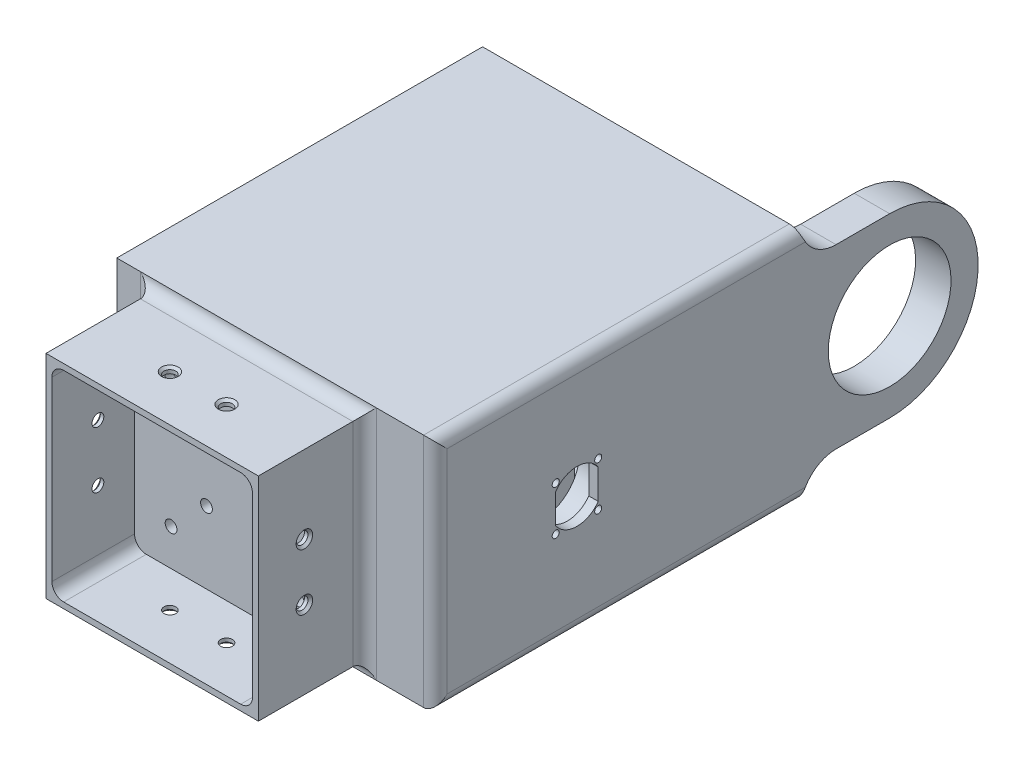
SolidWorks part; units mm, degrees
ref_plane "Front Plane" through (0, 0, 0) normal (0, 0, 1) x (1, 0, 0)
ref_plane "Top Plane" through (0, 0, 0) normal (0, 1, 0) x (1, 0, 0)
ref_plane "Right Plane" through (0, 0, 0) normal (1, 0, 0) x (0, 0, -1)
sketch "Sketch2" plane through (0, 0, 0) normal (0, 0, 1) x (1, 0, 0)
  line L1 (-45, 45) -> (45, 45)
  line L2 (-45, 45) -> (-45, -45)
  line L3 (-45, -45) -> (45, -45)
  line L4 (45, 45) -> (45, -45)
  line L5 (-45, 45) -> (45, -45) construction
  line L6 (-45, -45) -> (45, 45) construction
  point P0 (0, 0)
  dimension "D1" = 90
extrude "Boss-Extrude1" add sketch "Sketch2" along normal blind 45
sketch "Sketch3" plane through (0, 0, 45) normal (0, 0, 1) x (1, 0, 0)
  line L1 (-42.5, 42.5) -> (42.5, 42.5)
  line L2 (-42.5, 42.5) -> (-42.5, -42.5)
  line L3 (-42.5, -42.5) -> (42.5, -42.5)
  line L4 (42.5, 42.5) -> (42.5, -42.5)
  line L5 (-42.5, 42.5) -> (42.5, -42.5) construction
  line L6 (-42.5, -42.5) -> (42.5, 42.5) construction
  point P0 (0, 0)
  dimension "80" = 85
extrude "Cut-Extrude1" cut sketch "Sketch3" against normal blind 35
sketch "Sketch4" plane through (-45, 0, 0) normal (-1, 0, 0) x (0, 0, 1)
  line L0 (0, 45) -> (0, -45) construction
  line L3 (45, -45) -> (0, -45) construction
  circle A0 centre (25.5, 12) radius 2.5
  circle A1 centre (25.5, -12) radius 2.5
  dimension "D2" = 5
  dimension "D1" = 25.5
  dimension "D3" = 24
  dimension "D4" = 33
extrude "Cut-Extrude2" cut sketch "Sketch4" against normal through all
fillet "Fillet1" radius 5 4 edges at (42.5, -42.5, 27.5) (42.5, 42.5, 27.5) (-42.5, 42.5, 27.5) (-42.5, -42.5, 27.5)
sketch "Sketch5" plane through (0, 45, 0) normal (0, 1, 0) x (1, 0, 0)
  line L0 (45, 0) -> (-45, 0) construction
  line L1 (-45, -45) -> (-45, 0) construction
  circle A0 centre (-12, -25.5) radius 2.5
  circle A1 centre (12, -25.5) radius 2.5
  dimension "D3" = 5
  dimension "D1" = 24
  dimension "D2" = 25.5
  dimension "D4" = 33
extrude "Cut-Extrude3" cut sketch "Sketch5" against normal through all
chamfer "Chamfer1" distance 1 angle 45 8 edges at (12, 45, 28) (-12, 45, 28) (45, -14.5, 25.5) (45, 9.5, 25.5) (12, -45, 28) (-12, -45, 28) (-45, 9.5, 25.5) (-45, -14.5, 25.5)
sketch "Sketch7" plane through (0, 0, 0) normal (0, 0, -1) x (-1, 0, 0)
  line L1 (-75, 50) -> (75, 50)
  line L2 (-75, 50) -> (-75, -50)
  line L3 (-75, -50) -> (75, -50)
  line L4 (75, 50) -> (75, -50)
  line L5 (-75, 50) -> (75, -50) construction
  line L6 (-75, -50) -> (75, 50) construction
  point P0 (0, 0)
  dimension "D1" = 150
  dimension "D2" = 100
extrude "Boss-Extrude2" add sketch "Sketch7" along normal blind 155
sketch "Sketch8" plane through (0, 0, -155) normal (0, 0, -1) x (-1, 0, 0)
  line L1 (-60, 35) -> (60, 35)
  line L2 (-60, 35) -> (-60, -35)
  line L3 (-60, -35) -> (60, -35)
  line L4 (60, 35) -> (60, -35)
  line L5 (-60, 35) -> (60, -35) construction
  line L6 (-60, -35) -> (60, 35) construction
  point P0 (0, 0)
  dimension "D1" = 120
  dimension "D2" = 70
extrude "Cut-Extrude5" cut sketch "Sketch8" against normal blind 135
sketch "Sketch9" plane through (0, 0, 10) normal (0, 0, 1) x (1, 0, 0)
  line L0 (-41.0355, 41.0355) -> (41.0355, -41.0355) construction
  line L1 (41.0355, 41.0355) -> (-41.0355, -41.0355) construction
  line L2 (-42.5, 37.5) -> (-42.5, -37.5) construction
  arc A0 (-37.5, 42.5) -> (-42.5, 37.5) centre (-37.5, 37.5) ccw construction
  arc A1 (37.5, -42.5) -> (42.5, -37.5) centre (37.5, -37.5) ccw construction
  arc A2 (42.5, 37.5) -> (37.5, 42.5) centre (37.5, 37.5) ccw construction
  arc A3 (-42.5, -37.5) -> (-37.5, -42.5) centre (-37.5, -37.5) ccw construction
  circle A4 centre (-27, 27) radius 2.5
  circle A5 centre (27, 27) radius 2.5
  circle A6 centre (27, -27) radius 2.5
  circle A7 centre (-27, -27) radius 2.5
  circle A8 centre (-12, 12) radius 2.5
  circle A9 centre (12, 12) radius 2.5
  circle A10 centre (-12, -12) radius 2.5
  circle A11 centre (12, -12) radius 2.5
  dimension "D1" = 5
  dimension "D2" = 15.5
  dimension "D3" = 30.5
extrude "Cut-Extrude6" cut sketch "Sketch9" against normal through all
fillet "Fillet3" radius 5 4 edges at (0, -45, 0) (0, 45, 0) (-45, 0, 0) (45, 0, 0)
sketch "Sketch12" plane through (0, 0, -155) normal (0, 0, -1) x (-1, 0, 0)
  line L6 (-75, 0) -> (-60, 0) construction
  line L7 (-75, 50) -> (-75, -50) construction
  line L8 (-60, 35) -> (-60, -35) construction
  line L10 (-60, -37.5) -> (-75, -37.5)
  line L11 (-60, -37.5) -> (-60, 37.5)
  line L12 (-60, 37.5) -> (-75, 37.5)
  line L13 (-75, -37.5) -> (-75, 37.5)
  line L14 (-60, -37.5) -> (-75, 37.5) construction
  line L15 (-60, 37.5) -> (-75, -37.5) construction
  point P7 (-67.5, 0)
  dimension "D1" = 15
  dimension "D2" = 75
extrude "Boss-Extrude3" add sketch "Sketch12" along normal blind 75
sketch "Sketch13" plane through (60, 0, 0) normal (-1, 0, 0) x (0, 0, 1)
  line L0 (-230, -37.5) -> (-230, 37.5) construction
  line L1 (-230, 37.5) -> (-155, 37.5) construction
  circle A0 centre (-192.5, 0) radius 26
  dimension "D1" = 52
  dimension "D2" = 37.5
  dimension "D3" = 37.5
extrude "Cut-Extrude8" cut sketch "Sketch13" against normal blind 75
sketch "Sketch14" plane through (75, 0, 0) normal (1, 0, 0) x (0, 0, -1)
  line L0 (230, 37.5) -> (155, 37.5) construction
  line L1 (230, -37.5) -> (155, -37.5) construction
  line L2 (230, 37.5) -> (230, -37.5) construction
  arc A0 (192.5, 37.5) -> (192.5, -37.5) centre (192.5, 0) cw
  circle A1 centre (192.5, 0) radius 26 construction
  point P9 (230, 0)
extrude "Cut-Extrude9" cut sketch "Sketch14" against normal blind 75 and the other way through all
fillet "Fillet6" radius 15 2 edges at (67.5, -37.5, -155) (67.5, 37.5, -155)
fillet "Fillet7" radius 5 3 edges at (75, 0, 0) (75, -50, -77.5) (75, 50, -77.5)
sketch "Sketch15" plane through (0, 0, -155) normal (0, 0, -1) x (-1, 0, 0)
  line L0 (75, 50) -> (-60, 50) construction
  line L5 (75, -50) -> (60, -50)
  line L6 (75, -50) -> (75, 50)
  line L7 (75, 50) -> (60, 50)
  line L8 (60, -50) -> (60, 50)
  dimension "D1" = 15
extrude "Cut-Extrude11" cut sketch "Sketch15" against normal up to next
sketch "Sketch16" plane through (-60, 0, 0) normal (-1, 0, 0) x (0, 0, 1)
  line L0 (0, -50) -> (0, 50) construction
  line L1 (0, -50) -> (-155, -50) construction
  line L2 (0, 0) -> (-20, 0) construction
  line L3 (-20, -35) -> (-20, 35) construction
  circle A0 centre (-7.5, -42.5) radius 2
  circle A5 centre (-42.5, -42.5) radius 2
  circle A6 centre (-77.5, -42.5) radius 2
  circle A7 centre (-112.5, -42.5) radius 2
  circle A8 centre (-147.5, -42.5) radius 2
  circle A9 centre (-147.5, 42.5) radius 2
  circle A10 centre (-112.5, 42.5) radius 2
  circle A11 centre (-77.5, 42.5) radius 2
  circle A12 centre (-42.5, 42.5) radius 2
  circle A13 centre (-7.5, 42.5) radius 2
  circle A14 centre (-7.5, 12.5) radius 2
  circle A15 centre (-7.5, -17.5) radius 2
  dimension "D4" = 4
  dimension "D1" = 7.5
  dimension "D2" = 7.5
  dimension "D5" = 140
  dimension "D7" = 60
  dimension "D3" = 5
  dimension "D6" = 3
extrude "Cut-Extrude12" cut sketch "Sketch16" against normal blind 10
sketch "Sketch17" plane through (60, 0, 0) normal (-1, 0, 0) x (0, 0, 1)
  line L0 (-230, 0) -> (-20, 0) construction
  line L1 (-20, 35) -> (-20, -35) construction
  circle A0 centre (-60, 0) radius 13 construction
  arc A2 (-192.5, 37.5) -> (-192.5, -37.5) centre (-192.5, 0) ccw construction
  circle A4 centre (-69, 9.3808) radius 1.5
  circle A5 centre (-51, 9.3808) radius 1.5
  circle A6 centre (-51, -9.3808) radius 1.5
  circle A7 centre (-69, -9.3808) radius 1.5
  dimension "D1" = 26
  dimension "D4" = 3
  dimension "D2" = 40
  dimension "D3" = 9
extrude "Cut-Extrude13" cut sketch "Sketch17" against normal up to next
sketch "Sketch18" plane through (60, 0, 0) normal (-1, 0, 0) x (0, 0, 1)
  line L1 (-20, 35) -> (-20, -35) construction
  line L2 (-71, 0) -> (-49, 0) construction
  line L4 (-69, 6.3246) -> (-69, -6.3246)
  line L5 (-51, 6.3246) -> (-51, -6.3246)
  arc A0 (-69, -6.3246) -> (-51, -6.3246) centre (-60, 0) ccw
  arc A1 (-51, 6.3246) -> (-69, 6.3246) centre (-60, 0) ccw
  dimension "D1" = 22
  dimension "D2" = 9
  dimension "D3" = 40
  dimension "D4" = 18
extrude "Cut-Extrude15" cut sketch "Sketch18" against normal up to next
sketch "Sketch19" plane through (60, 0, 0) normal (-1, 0, 0) x (0, 0, 1)
  line L0 (-20, 35) -> (-20, -35) construction
  line L1 (-20, 0) -> (-91.0196, 0) construction
  circle A0 centre (-60, 0) radius 16
  dimension "D1" = 32
  dimension "D2" = 40
extrude "Cut-Extrude16" cut sketch "Sketch19" against normal blind 11
sketch "Sketch20" plane through (0, -35, 0) normal (0, 1, 0) x (1, 0, 0)
  line L0 (60, 20) -> (-60, 20) construction
  line L1 (50, 84) -> (30, 84)
  line L2 (50, 84) -> (50, 36)
  line L3 (50, 36) -> (30, 36)
  line L4 (30, 84) -> (30, 36)
  line L5 (50, 84) -> (30, 36) construction
  line L6 (50, 36) -> (30, 84) construction
  line L7 (60, 20) -> (60, 155) construction
  point P0 (40, 60)
  dimension "D1" = 40
  dimension "D2" = 48
  dimension "D3" = 20
  dimension "D4" = 10
extrude "Boss-Extrude4" add sketch "Sketch20" along normal blind 35
sketch "Sketch21" plane through (30, 0, 0) normal (-1, 0, 0) x (0, 0, 1)
  line L0 (-84, 0) -> (-36, 0) construction
  line L1 (-76, 0) -> (-44, 0)
  arc A0 (-76, 0) -> (-44, 0) centre (-60, 0) ccw
  dimension "D1" = 32
extrude "Cut-Extrude17" cut sketch "Sketch21" against normal up to next
sketch "Sketch22" plane through (0, 0, 0) normal (0, 1, 0) x (1, 0, 0)
  line L1 (50, 76) -> (30, 84) construction
  circle A1 centre (40, 80) radius 1.5
  point P0 (40, 80)
  dimension "D1" = 3
extrude "Cut-Extrude18" cut sketch "Sketch22" against normal blind 10
sketch "Sketch25" plane through (0, 0, 0) normal (0, 1, 0) x (1, 0, 0)
  line L0 (30, 44) -> (50, 36) construction
  circle A0 centre (40, 40) radius 1.5
  point P4 (40, 40)
  dimension "D1" = 3
extrude "Cut-Extrude19" cut sketch "Sketch25" against normal blind 10
sketch "Sketch26" plane through (0, -35, 0) normal (0, 1, 0) x (1, 0, 0)
  line L0 (60, 20) -> (-60, 20) construction
  line L1 (10, 84) -> (-5, 84)
  line L2 (10, 84) -> (10, 36)
  line L3 (10, 36) -> (-5, 36)
  line L4 (-5, 84) -> (-5, 36)
  line L5 (10, 84) -> (-5, 36) construction
  line L6 (10, 36) -> (-5, 84) construction
  line L7 (30, 84) -> (30, 36) construction
  point P0 (2.5, 60)
  dimension "D1" = 15
  dimension "D2" = 48
  dimension "D3" = 40
  dimension "D4" = 20
extrude "Boss-Extrude5" add sketch "Sketch26" along normal blind 35
sketch "Sketch27" plane through (-5, 0, 0) normal (-1, 0, 0) x (0, 0, 1)
  line L0 (-84, 0) -> (-36, 0) construction
  line L1 (-73.8, 0) -> (-46.2, 0)
  arc A0 (-73.8, 0) -> (-46.2, 0) centre (-60, 0) ccw
  dimension "D1" = 27.6
extrude "Cut-Extrude20" cut sketch "Sketch27" against normal up to next
sketch "Sketch29" plane through (0, 0, 0) normal (0, 1, 0) x (1, 0, 0)
  line L0 (10, 73.8) -> (-5, 84) construction
  circle A0 centre (2.5, 78.9) radius 1.5
  point P4 (2.5, 78.9)
  dimension "D1" = 3
extrude "Cut-Extrude21" cut sketch "Sketch29" against normal blind 10
ref_plane "Plane2" through (0, 0, -60) normal (0, 0, -1) x (-1, 0, 0)
mirror "Mirror3" about plane through (0, 0, -60) normal (0, 0, -1) of "Cut-Extrude21"
